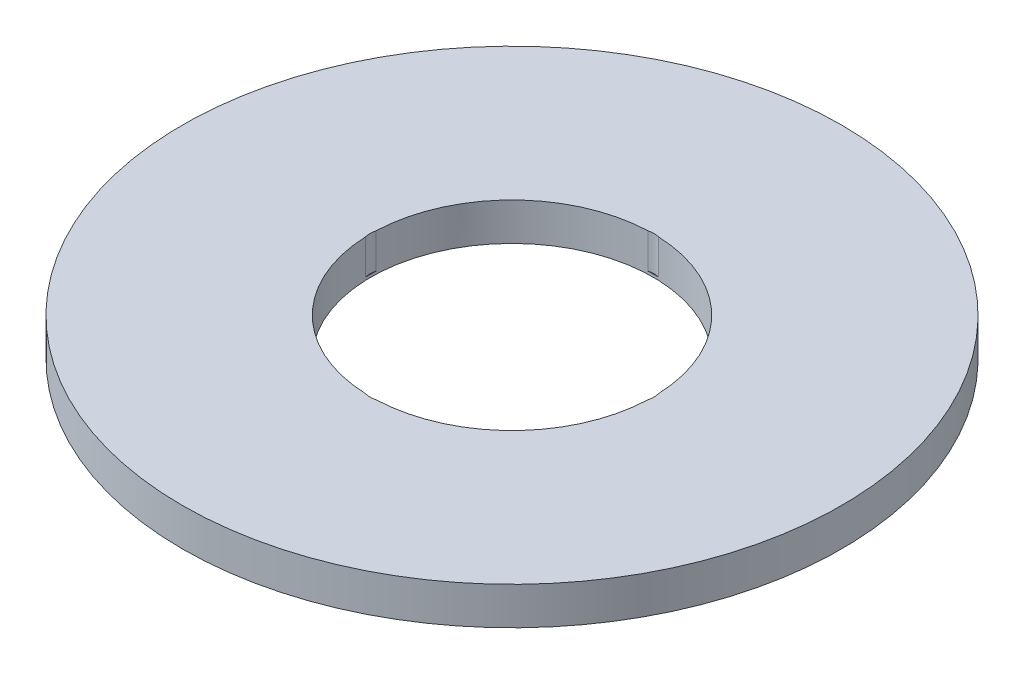
SolidWorks part; units mm, degrees
ref_plane "Front Plane" through (0, 0, 0) normal (0, 0, 1) x (1, 0, 0)
ref_plane "Top Plane" through (0, 0, 0) normal (0, 1, 0) x (1, 0, 0)
ref_plane "Right Plane" through (0, 0, 0) normal (1, 0, 0) x (0, 0, -1)
sketch "Sketch1" plane through (0, 0, 0) normal (0, 1, 0) x (1, 0, 0)
  circle A0 centre (0, 0) radius 70
  dimension "FLANGE_OD" = 140
extrude "Boss-Extrude1" add sketch "Sketch1" along normal blind 8
sketch "Sketch2" plane through (0, 0, 0) normal (0, 1, 0) x (1, 0, 0)
  circle A0 centre (0, 0) radius 30
  dimension "BORE_D" = 60
extrude "Cut-Extrude1" cut sketch "Sketch2" along normal through all
sketch "Sketch3" plane through (0, 8, 0) normal (0, 1, 0) x (1, 0, 0)
  circle A0 centre (0, 0) radius 26.0639 construction
  circle A1 centre (-26.0639, 0) radius 4.066
  dimension "BOLT_D" = 8.1319
  dimension "BOLT_PCD" = 52.1278
extrude "Cut-Extrude2" cut sketch "Sketch3" against normal blind 7.4201
pattern_circular "CirPattern1" count 4 over 360 about axis through (0, 0, 0) along (0, 1, 0) of "Cut-Extrude2"
